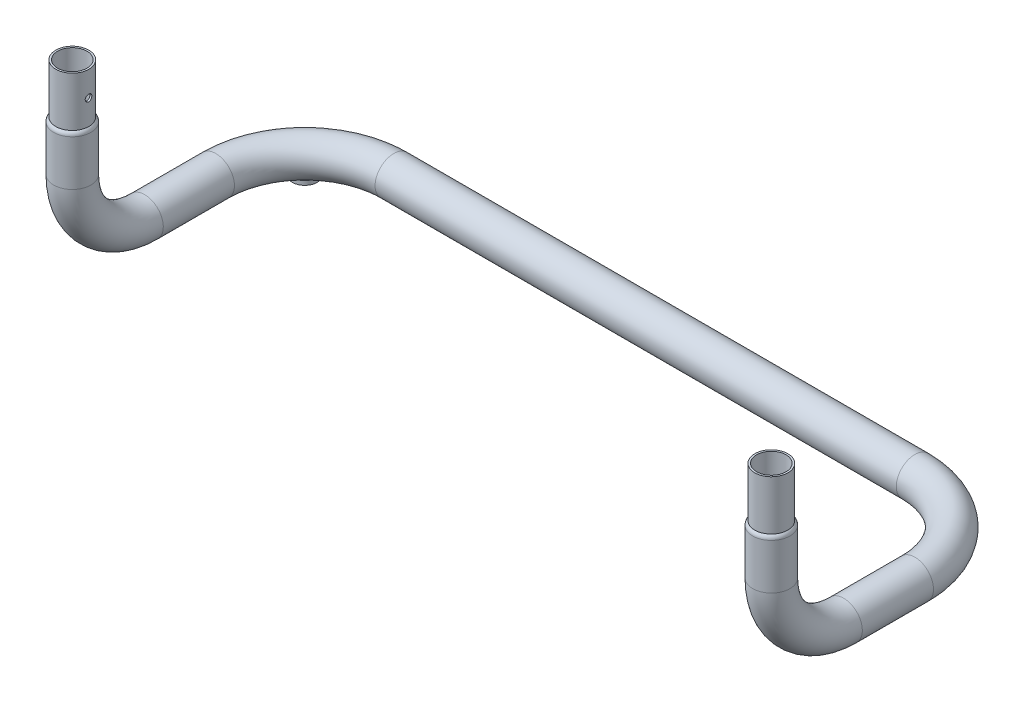
SolidWorks part; units mm, degrees
ref_plane "Front Plane" through (0, 0, 0) normal (0, 0, 1) x (1, 0, 0)
ref_plane "Top Plane" through (0, 0, 0) normal (0, 1, 0) x (1, 0, 0)
ref_plane "Right Plane" through (0, 0, 0) normal (1, 0, 0) x (0, 0, -1)
sketch3d "3DSketch2"
  line L0 (-157.5, 0, 0) -> (157.5, 0, 0)
  line L1 (222.5, 0, 65) -> (222.5, 0, 108)
  line L2 (222.5, 55, 163) -> (222.5, 85, 163)
  line L3 (-222.5, 55, 163) -> (-222.5, 85, 163)
  line L4 (-222.5, 0, 65) -> (-222.5, 0, 108)
  arc A0 (157.5, 0, 0) -> (222.5, 0, 65) centre (157.5, 0, 65) ccw
  arc A1 (222.5, 0, 108) -> (222.5, 55, 163) centre (222.5, 55, 108) ccw
  arc A2 (-222.5, 55, 163) -> (-222.5, 0, 108) centre (-222.5, 55, 108) cw
  arc A3 (-222.5, 0, 65) -> (-157.5, 0, 0) centre (-157.5, 0, 65) cw
  point P3 (-222.5, 55, 163)
  point P4 (0, 0, 0)
  point P9 (222.5, 0, 0)
  point P10 (157.5, -65, 65)
  point P13 (222.5, 0, 163)
  point P14 (167.5, 55, 108)
  point P15 (0, 0, 0)
  point P16 (0, 0, 0)
  point P17 (-146.3367, 0, 0)
  point P22 (-167.5, 55, 108)
  point P25 (-157.5, -65, 65)
  point P26 (222.5, 55, 163)
  point P27 (0, 0, 0)
  point P28 (-222.5, 55, 108)
  dimension "D4" = 65
  dimension "D5" = 55
  dimension "D1" = 445
  dimension "D2" = 163
  dimension "D3" = 85
ref_plane "Plane4" through (0, 85, 0) normal (0, 1, 0) x (1, 0, 0)
sketch "Sketch1" plane through (0, 85, 0) normal (0, 1, 0) x (1, 0, 0)
  line L1 (200, -140.5) -> (222.5, -140.5) construction
  line L2 (200, -140.5) -> (200, -163) construction
  line L3 (200, -163) -> (222.5, -163) construction
  line L4 (222.5, -140.5) -> (222.5, -163) construction
  line L5 (200, -140.5) -> (222.5, -163) construction
  line L6 (200, -163) -> (222.5, -140.5) construction
  circle A0 centre (211.25, -151.75) radius 11.25
  circle A1 centre (211.25, -151.75) radius 10.15
  point P4 (0, 0)
  dimension "D1" = 22.5
  dimension "D2" = 1.1
sweep "Sweep1" add profiles "Sketch1" path "3DSketch2"
sketch "Sketch2" plane through (0, 85, 0) normal (0, 1, 0) x (1, 0, 0)
  circle A0 centre (211.25, -151.75) radius 10 construction
  circle A2 centre (211.25, -151.75) radius 8.9
  circle A4 centre (211.25, -151.75) radius 11.25
  circle A5 centre (211.25, -151.75) radius 11.25
  dimension "D1" = 20
  dimension "D2" = 1.1
  dimension "D3" = 0
extrude "Boss-Extrude1" add sketch "Sketch2" against normal blind 1.1
sketch "Sketch3" plane through (0, 85, 0) normal (0, 1, 0) x (1, 0, 0)
  circle A0 centre (211.25, -151.75) radius 8.9 construction
  circle A1 centre (211.25, -151.75) radius 8.9
  circle A2 centre (211.25, -151.75) radius 10
  dimension "D1" = 20
extrude "Boss-Extrude2" add sketch "Sketch3" along normal offset from surface (30 mm away) 115 up to plane "Top Plane"
mirror "Mirror7" about plane through (0, 0, 0) normal (1, 0, 0) of "Boss-Extrude2", "Boss-Extrude1"
fillet "Fillet1" radius 3 4 edges at (211.25, 83.9, 161.9) (211.25, 85, 163) (-211.25, 85, 163) (-211.25, 83.9, 161.9)
sketch "Sketch4" plane through (0, 0, 0) normal (0, 1, 0) x (1, 0, 0)
  line L0 (187.552, -34.948) -> (203.4619, -19.0381) construction
  arc A0 (222.5, -65) -> (157.5, 0) centre (157.5, -65) ccw construction
  arc A1 (222.5, -65) -> (157.5, 0) centre (157.5, -65) ccw construction
  arc A2 (200, -65) -> (157.5, -22.5) centre (157.5, -65) ccw construction
  arc A3 (200, -65) -> (157.5, -22.5) centre (157.5, -65) ccw construction
  circle A4 centre (195.507, -26.993) radius 5
  circle A5 centre (195.507, -26.993) radius 7.5 construction
  dimension "D1" = 10
  dimension "D2" = 15
extrude "Cut-Extrude1" cut sketch "Sketch4" along normal up to next contours A4
sketch "Sketch5" plane through (0, 0, 0) normal (0, 1, 0) x (1, 0, 0)
  circle A0 centre (195.507, -26.993) radius 7.5 construction
  circle A1 centre (195.507, -26.993) radius 7.5
  circle A2 centre (195.507, -26.993) radius 4.75
  dimension "D1" = 9.5
extrude "Boss-Extrude3" add sketch "Sketch5" along normal blind 2.5
ref_plane "Plane5" through (201.25, 0, 0) normal (-1, 0, 0) x (0, 0, 1)
sketch "Sketch6" plane through (201.25, 0, 0) normal (-1, 0, 0) x (0, 0, 1)
  line L0 (161.75, 115) -> (141.75, 115) construction
  line L1 (161.75, 115) -> (141.75, 115) construction
  line L2 (151.75, 115) -> (151.75, 100) construction
  circle A0 centre (151.75, 100) radius 2
  dimension "D1" = 4
  dimension "D2" = 15
extrude "Cut-Extrude2" cut sketch "Sketch6" against normal blind 2.5
mirror "Mirror8" about plane through (0, 0, 0) normal (1, 0, 0) of "Cut-Extrude2", "Cut-Extrude1", "Boss-Extrude3"
